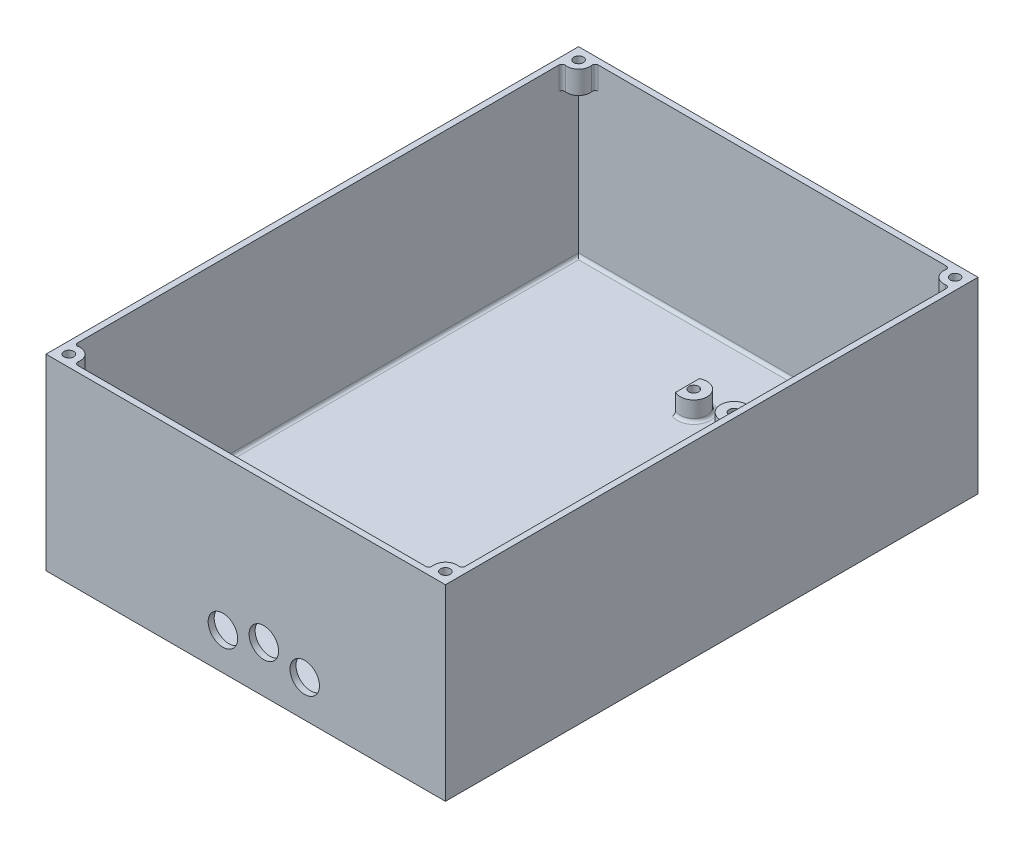
SolidWorks part; units mm, degrees
ref_plane "Front Plane" through (0, 0, 0) normal (0, 0, 1) x (1, 0, 0)
ref_plane "Top Plane" through (0, 0, 0) normal (0, 1, 0) x (1, 0, 0)
ref_plane "Right Plane" through (0, 0, 0) normal (1, 0, 0) x (0, 0, -1)
sketch "Sketch2" plane through (0, 0, 0) normal (0, 1, 0) x (1, 0, 0)
  line L0 (-101.6, 136.525) -> (101.6, 136.525)
  line L1 (-104.775, -139.7) -> (104.775, -139.7)
  line L2 (-104.775, -139.7) -> (-104.775, 139.7)
  line L3 (-104.775, 139.7) -> (104.775, 139.7)
  line L4 (104.775, -139.7) -> (104.775, 139.7)
  line L5 (-104.775, -139.7) -> (104.775, 139.7) construction
  line L6 (-104.775, 139.7) -> (104.775, -139.7) construction
  line L7 (101.6, -136.525) -> (101.6, 136.525)
  line L8 (-101.6, -136.525) -> (101.6, -136.525)
  line L9 (-101.6, -136.525) -> (-101.6, 136.525)
  point P0 (0, 0)
  dimension "D2" = 203.2
  dimension "D3" = 273.05
  dimension "D1" = 3.175
extrude "Box Base" add sketch "Sketch2" along normal blind 6.35 contours L9 L8 L7 L0 region at (0, 0, 0)
extrude "Box Wall height" add sketch "Sketch2<3>" along normal blind 98.425
sketch "Sketch2<3>" plane through (0, 0, 0) normal (0, 1, 0) x (1, 0, 0) same geometry as "Sketch2"
sketch "Sketch9" plane through (0, 98.425, 0) normal (0, 1, 0) x (1, 0, 0)
  line L0 (-104.775, 139.7) -> (-86.8145, 121.7395) construction
  line L1 (104.775, 139.7) -> (-104.775, 139.7) construction
  line L2 (101.6, 136.525) -> (-101.6, 136.525) construction
  line L3 (-101.6, -136.525) -> (-101.6, 136.525) construction
  line L4 (-101.6, 128.4067) -> (-104.775, 128.4067)
  line L5 (-104.775, 139.7) -> (-104.775, -139.7) construction
  line L6 (-104.775, 128.4067) -> (-104.775, 139.7)
  line L7 (-104.775, 139.7) -> (-93.4817, 139.7)
  line L8 (-93.4817, 139.7) -> (-93.4817, 136.525)
  line L9 (0, 166.2937) -> (0, -171.0514) construction
  line L10 (-137.4993, 0) -> (136.9788, 0) construction
  line L11 (104.775, 139.7) -> (86.8145, 121.7395) construction
  line L12 (93.4817, 139.7) -> (93.4817, 136.525)
  line L13 (104.775, 139.7) -> (93.4817, 139.7)
  line L14 (104.775, 128.4067) -> (104.775, 139.7)
  line L15 (101.6, 128.4067) -> (104.775, 128.4067)
  line L16 (104.775, -139.7) -> (86.8145, -121.7395) construction
  line L17 (-104.775, -139.7) -> (-86.8145, -121.7395) construction
  line L18 (101.6, -128.4067) -> (104.775, -128.4067)
  line L19 (104.775, -128.4067) -> (104.775, -139.7)
  line L20 (104.775, -139.7) -> (93.4817, -139.7)
  line L21 (93.4817, -139.7) -> (93.4817, -136.525)
  line L22 (-93.4817, -139.7) -> (-93.4817, -136.525)
  line L23 (-104.775, -139.7) -> (-93.4817, -139.7)
  line L24 (-104.775, -128.4067) -> (-104.775, -139.7)
  line L25 (-101.6, -128.4067) -> (-104.775, -128.4067)
  circle A0 centre (-98.775, 133.7) radius 2.5273
  arc A1 (-93.4817, 136.525) -> (-101.6, 128.4067) centre (-98.775, 133.7) cw
  arc A2 (93.4817, 136.525) -> (101.6, 128.4067) centre (98.775, 133.7) ccw
  circle A3 centre (98.775, 133.7) radius 2.5273
  circle A4 centre (98.775, -133.7) radius 2.5273
  arc A5 (93.4817, -136.525) -> (101.6, -128.4067) centre (98.775, -133.7) cw
  arc A6 (-93.4817, -136.525) -> (-101.6, -128.4067) centre (-98.775, -133.7) ccw
  circle A7 centre (-98.775, -133.7) radius 2.5273
  line M2 (104.775, -139.7) -> (104.775, 139.7)
  line M3 (104.775, 139.7) -> (-104.775, 139.7)
  line M4 (-104.775, 139.7) -> (-104.775, -139.7)
  line M5 (-104.775, -139.7) -> (104.775, -139.7)
  line M6 (-101.6, -136.525) -> (-101.6, 136.525)
  line M7 (-101.6, 136.525) -> (101.6, 136.525)
  line M8 (101.6, 136.525) -> (101.6, -136.525)
  line M9 (101.6, -136.525) -> (-101.6, -136.525)
  dimension "D2" = 5.0546
  dimension "D4" = 6
  dimension "D1" = 25.4
  dimension "D3" = 6
extrude "Boss-Extrude4" add sketch "Sketch9" against normal blind 12 contours A7 | A6 A7 M9 M6 | L25 L22 M6 M4 M5 M9 | A5 A4 M9 M8 | A4 | L21 L18 M5 M2 M8 M9 | L15 L12 M8 M2 M3 M7 | A3 | A2 A3 M7 M8 | A0 | A1 A0 M7 M6 | L8 L4 M3 M4 M6 M7 region at (-101.4752, 98.425, -132.4658) region at (-103.1875, 98.425, -128.5664) region at (-101.7597, 98.425, 132.4658) region at (-94.6206, 98.425, 129.5456) region at (97.5408, 98.425, -136.4002) region at (93.6414, 98.425, -138.1125) region at (97.5408, 98.425, 136.6847) region at (94.6206, 98.425, 129.5456) region at (-98.775, 98.425, -133.7) region at (98.775, 98.425, -133.7) region at (98.775, 98.425, 133.7) region at (-98.775, 98.425, 133.7)
fillet "Fillet2" radius 1.5875 8 edges at (-93.4817, 92.425, 136.525) (-101.6, 92.425, 128.4067) (93.4817, 92.425, 136.525) (101.6, 92.425, 128.4067) (93.4817, 92.425, -136.525) (101.6, 92.425, -128.4067) (-93.4817, 92.425, -136.525) (-101.6, 92.425, -128.4067)
hole_wizard "Lid Mounting heat Set Insert Holes" positions "Sketch12" profile "Sketch13" hole size "#8" standard "ANSI Inch"
sketch "Sketch12" plane through (0, 98.425, 0) normal (0, 1, 0) x (1, 0, 0)
  arc A0 (99.7536, -127.7803) -> (92.8553, -134.6786) centre (98.775, -133.7) ccw construction
  arc A1 (-92.8553, -134.6786) -> (-99.7536, -127.7803) centre (-98.775, -133.7) ccw construction
  arc A2 (-99.7536, 127.7803) -> (-92.8553, 134.6786) centre (-98.775, 133.7) ccw construction
  arc A3 (92.8553, 134.6786) -> (99.7536, 127.7803) centre (98.775, 133.7) ccw construction
  point P0 (98.775, 133.7)
  point P2 (-98.775, 133.7)
  point P4 (-98.775, -133.7)
  point P6 (98.775, -133.7)
sketch "Sketch13" plane through (98.775, 98.425, -133.7) normal (1, 0, 0) x (0, 0, 1)
  line L0 (0, 0) -> (0, 10.4086)
  line L1 (0, 10.4086) -> (2.5273, 8.89)
  line L2 (2.5273, 8.89) -> (2.5273, 0)
  line L5 (2.5273, 0) -> (0, 0)
  line L10 (0, 10.4086) -> (-2.5273, 8.89) construction
  line L11 (0, -6.35) -> (0, 107.95) construction
  dimension "Hole Dia." = 5.0546
  dimension "Hole Depth" = 8.89
  dimension "Drill Angle" = 118
sketch "Sketch14" plane through (0, 6.35, 0) normal (0, 1, 0) x (1, 0, 0)
  line L0 (-14.3506, -103.759) -> (33.3506, -103.759) construction
  line L5 (33.3506, -103.759) -> (33.3506, 102.743) construction
  line L6 (33.3506, 102.743) -> (-14.3506, 102.743) construction
  line L7 (-14.3506, 102.743) -> (-14.3506, -103.759) construction
  line L24 (97.2, -91.7339) -> (97.2, -47.7339) construction
  line L25 (97.2, -69.7339) -> (-97.2, -69.7339) construction
  line L26 (-97.2, -91.7339) -> (-97.2, -47.7339) construction
  line L27 (97.2, -47.7339) -> (-97.2, -47.7339) construction
  line L28 (-1.041, 96.393) -> (20.041, 96.393) construction
  line L29 (97.2, -91.7339) -> (-97.2, -91.7339) construction
  line L30 (-4.343, -103.5813) -> (-4.343, 102.5653)
  line L31 (9.5, 83.75) -> (9.5, 97.9206) construction
  line L32 (23.343, -103.5813) -> (23.343, 102.5653)
  line L33 (-29.3379, -103.759) -> (14.3293, -103.759) construction
  line L36 (-91.2891, -136.525) -> (91.2891, -136.525) construction
  line L37 (-7.366, -121.539) -> (34.6464, -121.539) construction
  line L39 (-18.9436, -131.699) -> (51.3952, -131.699) construction
  line L41 (-18.9436, -93.599) -> (51.3952, -93.599) construction
  circle A10 centre (28.5, -89.2339) radius 1.25 construction
  circle A11 centre (-9.5, -72.2339) radius 1.25 construction
  circle A12 centre (20.041, -97.409) radius 2.2606 construction
  circle A13 centre (-1.041, -97.409) radius 2.2606 construction
  circle A14 centre (20.041, 96.393) radius 2.2606 construction
  circle A15 centre (-1.041, 96.393) radius 2.2606 construction
  circle A16 centre (28.5, -50.2339) radius 1.65 construction
  circle A17 centre (-9.5, -67.2339) radius 1.65 construction
  circle A18 centre (-9.5, -72.2339) radius 1.65 construction
  circle A19 centre (28.5, -89.2339) radius 1.65 construction
  circle A20 centre (-1.041, -97.409) radius 2.5273
  circle A21 centre (20.041, -97.409) radius 2.5273
  circle A22 centre (20.041, 96.393) radius 2.5273
  circle A23 centre (-1.041, 96.393) radius 2.5273
  arc A24 (-4.343, -103.5813) -> (-4.343, -91.2367) centre (-1.041, -97.409) ccw
  arc A25 (23.343, -91.2367) -> (23.343, -103.5813) centre (20.041, -97.409) ccw
  arc A26 (-4.343, 90.2207) -> (-4.343, 102.5653) centre (-1.041, 96.393) ccw
  arc A27 (23.343, 102.5653) -> (23.343, 90.2207) centre (20.041, 96.393) ccw
  point P49 (0, -136.525)
  point P50 (0, -47.7339)
  point P55 (-1.041, -93.0085)
  dimension "D11" = 4.5212
  dimension "D18" = 3.3
  dimension "D19" = 5.0546
  dimension "D20" = 14
  dimension "D1" = 47.7012
  dimension "D2" = 206.502
  dimension "D3" = 21.082
  dimension "D4" = 6.35
  dimension "D5" = 13.3096
  dimension "D6" = 4.8506
  dimension "D7" = 31.5251
  dimension "D8" = 14.5251
  dimension "D9" = 4.8506
  dimension "D10" = 6.35
  dimension "D12" = 22
  dimension "D13" = 194.4
  dimension "D14" = 87.7
  dimension "D15" = 2.5
  dimension "D16" = 125.7
  dimension "D17" = 19.5
  dimension "D21" = 3.302
  dimension "D22" = 6.35
  dimension "D23" = 14.986
  dimension "D24" = 10.16
  dimension "D25" = 38.1
  dimension "D26" = 10.16
extrude "MME-42 Mounting Pegs" add sketch "Sketch14" along normal blind 10 contours L30 A24 A20 | L32 A25 A21 | L30 A26 A23 | L32 A27 A22 region at (-4.1692, 6.35, -96.393) region at (-4.1692, 6.35, 97.409) region at (13.2148, 6.35, 97.409) region at (13.2148, 6.35, -96.393)
fillet "Fillet3" radius 1.5875 4 edges at (5.959, 6.35, -96.393) (13.041, 6.35, -96.393) (13.041, 6.35, 97.409) (5.959, 6.35, 97.409)
fillet "Fillet5" radius 1.5875 4 edges at (0, 6.35, 136.525) (101.6, 6.35, 0) (-101.6, 6.35, 0) (0, 6.35, -136.525)
sketch "Sketch18" plane through (0, 98.425, 0) normal (0, 1, 0) x (1, 0, 0)
  line L4 (-104.775, 139.7) -> (-104.775, -139.7)
  line L5 (-104.775, -139.7) -> (104.775, -139.7)
  line L6 (104.775, -139.7) -> (104.775, 139.7)
  line L7 (104.775, 139.7) -> (-104.775, 139.7)
  line L8 (-104.775, 139.7) -> (-104.775, -139.7)
  line L9 (-104.775, -139.7) -> (104.775, -139.7)
  line L10 (104.775, -139.7) -> (104.775, 139.7)
  line L11 (104.775, 139.7) -> (-104.775, 139.7)
  circle A0 centre (-98.775, -133.7) radius 2.5273 construction
  circle A1 centre (-98.775, -133.7) radius 2.5273
  circle A2 centre (-98.775, 133.7) radius 2.5273 construction
  circle A3 centre (-98.775, 133.7) radius 2.5273
  circle A4 centre (98.775, -133.7) radius 2.5273 construction
  circle A5 centre (98.775, 133.7) radius 2.5273 construction
  circle A6 centre (98.775, -133.7) radius 2.5273
  circle A7 centre (98.775, 133.7) radius 2.5273
  dimension "D1" = 0
sketch "Sketch19" plane through (0, 0, 139.7) normal (0, 0, 1) x (1, 0, 0)
  circle A0 centre (-11.963, 19.398) radius 6.955 construction
  circle A1 centre (9.5, 24.478) radius 6.955 construction
  circle A2 centre (30.963, 19.398) radius 6.955 construction
  circle A3 centre (-11.963, 19.398) radius 6.955
  circle A4 centre (9.5, 24.478) radius 6.955
  circle A5 centre (30.963, 19.398) radius 6.955
  circle A6 centre (-11.963, 19.398) radius 7.7391
  circle A7 centre (9.5, 24.478) radius 7.7391
  circle A8 centre (30.963, 19.398) radius 7.7391
  dimension "D1" = 15.4781
extrude "Cut-Extrude2" cut sketch "Sketch19" against normal up to surface (3.175 mm away) contours A6 | A7 | A8 up to face at (0, 69.8031, 136.525)
